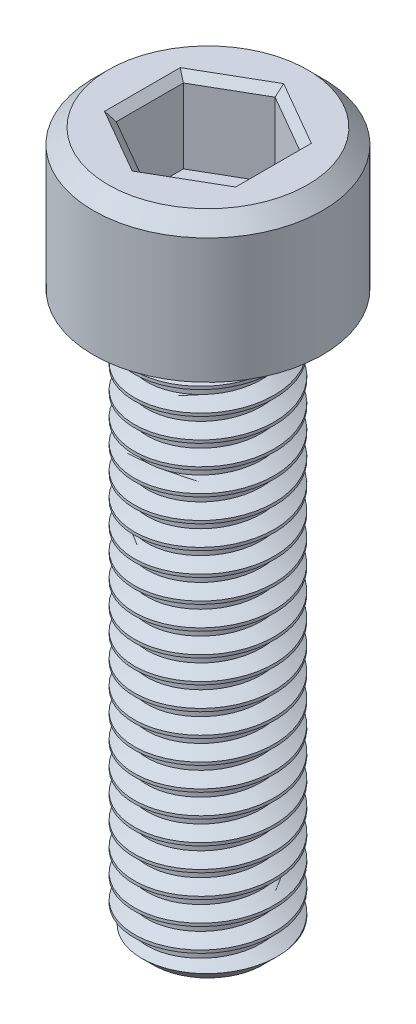
SolidWorks part; units mm, degrees
material "Plain Carbon Steel"
ref_plane "Front Plane" through (0, 0, 0) normal (0, 0, 1) x (1, 0, 0)
ref_plane "Top Plane" through (0, 0, 0) normal (0, 1, 0) x (1, 0, 0)
ref_plane "Right Plane" through (0, 0, 0) normal (1, 0, 0) x (0, 0, -1)
ref_plane "Plane1" through (0, 0, 0) normal (0, 0, -1) x (-1, 0, 0)
sketch "Sketch1" plane through (0, 0, 0) normal (0, 0, -1) x (-1, 0, 0)
  line L0 (-3.9116, -4.7752) -> (0, -4.7752)
  line L1 (0, -4.7752) -> (0, 0)
  line L2 (0, 0) -> (-3.9116, 0)
  line L3 (-3.9116, 0) -> (-3.9116, -4.7752)
  line L4 (0, -4.7752) -> (0, 0) construction
revolve "Revolve1" add sketch "Sketch1" angle 360 about L4 reverse direction yes
sketch "Sketch2" plane through (0, -4.7752, 0) normal (0, -1, 0) x (1, 0, 0)
  circle A0 centre (0, 0) radius 2.3876
extrude "Boss-Extrude1" add sketch "Sketch2" along normal blind 19.05
sketch "Sketch3" plane through (0, 0, 0) normal (0, 1, 0) x (-1, 0, 0)
  line L0 (1.9844, -1.1457) -> (1.9844, 1.1457)
  line L1 (1.9844, 1.1457) -> (0, 2.2914)
  line L2 (0, 2.2914) -> (-1.9844, 1.1457)
  line L3 (-1.9844, 1.1457) -> (-1.9844, -1.1457)
  line L4 (-1.9844, -1.1457) -> (0, -2.2914)
  line L5 (0, -2.2914) -> (1.9844, -1.1457)
extrude "Cut-Extrude1" cut sketch "Sketch3" against normal blind 2.794
chamfer "Chamfer1" distance 0.508 angle 45 2 edges at (0, -23.8252, -2.3876) (0, 0, 3.9116)
chamfer "Chamfer2" distance 0.254 angle 45 6 edges at (-0.9922, 0, -1.7185) (-1.9844, 0, 0) (0.9922, 0, -1.7185) (-0.9922, 0, 1.7185) (1.9844, 0, 0) (0.9922, 0, 1.7185)
thread "Thread1" pitch 0.7937 method cut profile "Thread Profile1" start angle 0, offset 0, length 0, pitch 0.7937, diameter 4.7752
ref_plane "Plane2" through (-2.3876, -4.7752, 0) normal (0, 0, 1) x (-1, 0, 0)
sketch "Thread Profile1" plane through (-2.3876, -4.7752, 0) normal (0, 0, 1) x (-1, 0, 0)
  line L0 (0, 0) -> (0, 0.7937) construction
  line L11 (0, 0) -> (0, 0.6945)
  line L12 (0, 0.6945) -> (-0.4296, 0.4465)
  line L13 (-0.4296, 0.4465) -> (-0.4296, 0.248)
  line L15 (-0.4296, 0.248) -> (0, 0)
  line L17 (-0.4296, 0.3473) -> (0, 0.3473) construction
  point P2 (0, 0)
  dimension "Pitch" = 0.7937
  dimension "Profile_Angle" = 60
  dimension "Profile_Land" = 0.1984
  dimension "Profile_Height" = 0.4296
